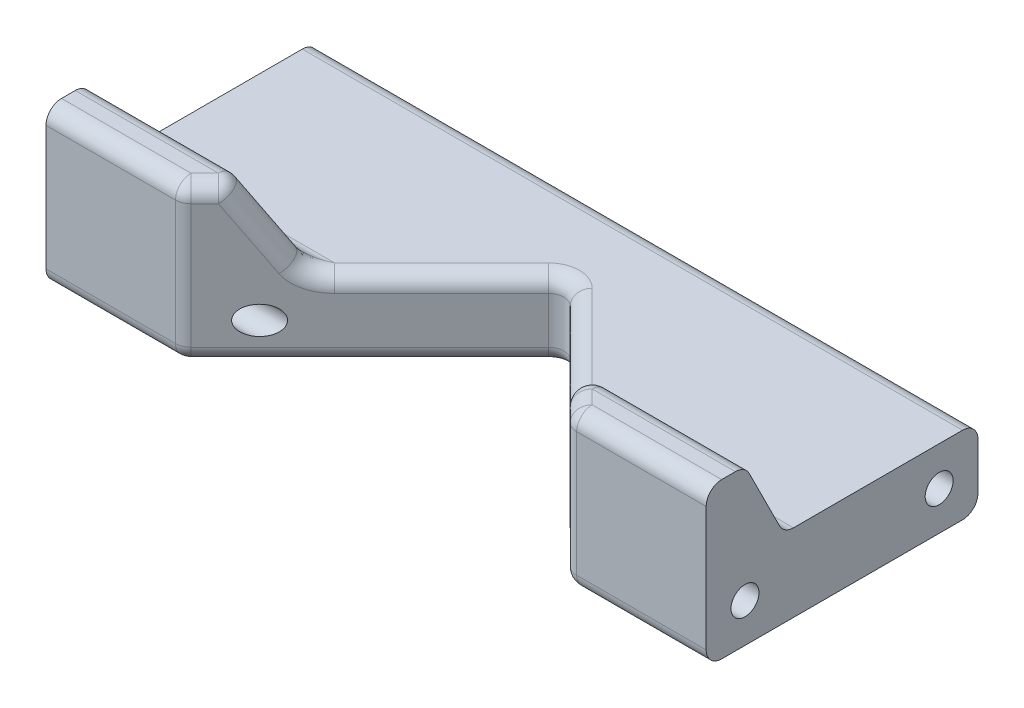
SolidWorks part; units mm, degrees
ref_plane "Front Plane" through (0, 0, 0) normal (0, 0, 1) x (1, 0, 0)
ref_plane "Top Plane" through (0, 0, 0) normal (0, 1, 0) x (1, 0, 0)
ref_plane "Right Plane" through (0, 0, 0) normal (1, 0, 0) x (0, 0, -1)
sketch "Sketch1" plane through (0, 0, 0) normal (1, 0, 0) x (0, 0, -1)
  line L0 (-44.45, 12.7) -> (-44.45, 25.4)
  line L1 (0, 0) -> (-44.45, 0)
  line L2 (0, 0) -> (0, 12.7)
  line L3 (0, 12.7) -> (-31.75, 12.7)
  line L4 (-44.45, 0) -> (-44.45, 12.7)
  line L5 (-44.45, 25.4) -> (-38.1, 25.4)
  line L6 (-38.1, 25.4) -> (-31.75, 12.7)
  circle A0 centre (-6.35, 6.35) radius 2.286
  circle A1 centre (-38.1, 6.35) radius 2.286
  point P10 (0, 6.35)
  point P13 (0, 0)
  point P14 (0, 0)
  dimension "D4" = 4.572
  dimension "D1" = 31.75
  dimension "D2" = 6.35
  dimension "D3" = 12.7
  dimension "D5" = 6.35
  dimension "D6" = 12.7
  dimension "D7" = 12.7
  dimension "D8" = 6.35
extrude "Boss-Extrude1" add sketch "Sketch1" along normal blind 107.95
fillet "Fillet1" radius 2.54 6 edges at (53.975, 12.7, 31.75) (53.975, 25.4, 44.45) (53.975, 25.4, 38.1) (53.975, 0, 44.45) (53.975, 0, 0) (53.975, 12.7, 0)
sketch "Sketch2" plane through (0, 0, 0) normal (0, -1, 0) x (1, 0, 0)
  line L1 (22.225, 44.45) -> (53.975, 12.7)
  line L2 (0, 44.45) -> (107.95, 44.45) construction
  line L3 (53.975, 12.7) -> (53.975, 44.45) construction
  line L4 (85.725, 44.45) -> (22.225, 44.45)
  line L5 (85.725, 44.45) -> (53.975, 12.7)
  dimension "D1" = 31.75
  dimension "D2" = 31.75
extrude "Cut-Extrude1" cut sketch "Sketch2" against normal through all
fillet "Fillet2" radius 2.54 19 edges at (82.0649, 25.4, 40.7899) (79.6094, 25.0207, 38.3344) (84.9811, 24.6561, 43.7061) (76.2, 19.05, 34.925) (85.725, 12.7, 44.45) (72.7906, 13.0793, 31.5156) (84.9811, 0.7439, 43.7061) (62.7151, 12.7, 21.4401) (68.58, 0, 27.305) (45.2349, 12.7, 21.4401) (35.1594, 13.0793, 31.5156) (31.75, 19.05, 34.925) (28.3406, 25.0207, 38.3344) (25.8851, 25.4, 40.7899) (22.9689, 24.6561, 43.7061) (39.37, 0, 27.305) (22.9689, 0.7439, 43.7061) (22.225, 12.7, 44.45) (53.975, 6.35, 12.7)
